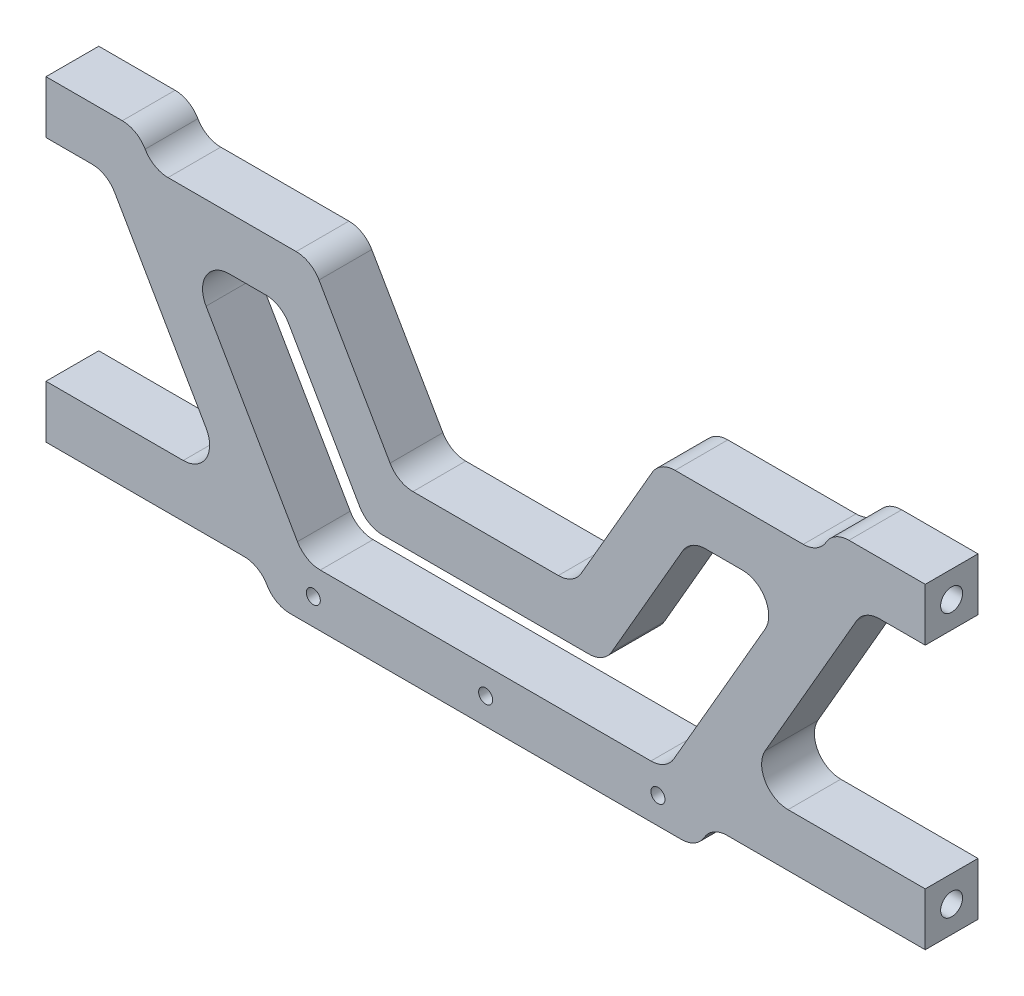
SolidWorks part; units mm, degrees
ref_plane "Front Plane" through (0, 0, 0) normal (0, 0, 1) x (1, 0, 0)
ref_plane "Top Plane" through (0, 0, 0) normal (0, 1, 0) x (1, 0, 0)
ref_plane "Right Plane" through (0, 0, 0) normal (1, 0, 0) x (0, 0, -1)
sketch "Sketch1" plane through (0, 0, 0) normal (0, 0, 1) x (1, 0, 0)
  line L1 (-50, 0) -> (50, 0)
  line L2 (-50, 0) -> (-50, 39)
  line L3 (-50, 39) -> (50, 39)
  line L4 (50, 0) -> (50, 39)
  dimension "D1" = 39
  dimension "D2" = 100
extrude "Boss-Extrude1" add sketch "Sketch1" along normal blind 6
sketch "Sketch2" plane through (0, 0, 6) normal (0, 0, 1) x (1, 0, 0)
  line L0 (-50, 33) -> (-43.0526, 33)
  line L2 (-50, 39) -> (-50, 0) construction
  line L3 (-43.0526, 33) -> (-29.1962, 9)
  line L5 (-29.1962, 9) -> (-50, 9)
  line L6 (-50, 9) -> (-50, 33)
  line L7 (50, 39) -> (-50, 39) construction
  line L8 (-39.5885, 39) -> (-37.8564, 36)
  line L9 (-10, 19) -> (0, 19)
  line L10 (0, 19) -> (0, 39)
  line L11 (0, 39) -> (-39.5885, 39)
  line L12 (-50, 3) -> (-25.7321, 3)
  line L13 (-25.7321, 3) -> (-24, 0)
  line L14 (-50, 0) -> (50, 0) construction
  line L15 (-24, 0) -> (-50, 0)
  line L16 (-50, 0) -> (-50, 3)
  line L17 (-13.4641, 13) -> (0, 13)
  line L18 (0, 13) -> (0, 6)
  line L19 (0, 6) -> (-20.5359, 6)
  line L20 (-20.5359, 6) -> (-34.3923, 30)
  line L21 (-37.8564, 36) -> (-19.815, 36)
  line L22 (-19.815, 36) -> (-10, 19)
  line L23 (-13.4641, 13) -> (-23.2791, 30)
  line L24 (-23.2791, 30) -> (-34.3923, 30)
  dimension "D3" = 60
  dimension "D1" = 6
  dimension "D2" = 24
  dimension "D4" = 6
  dimension "D5" = 3
  dimension "D6" = 24
  dimension "D7" = 6
  dimension "D8" = 6
  dimension "D9" = 3
  dimension "D10" = 6
  dimension "D11" = 6
  dimension "D12" = 20
  dimension "D13" = 10
extrude "Cut-Extrude1" cut sketch "Sketch2" against normal up to next
hole_wizard "Tap Drill for M3 Tap1" positions "Sketch4" profile "Sketch3" hole size "M3" standard "ISO"
sketch "Sketch4" plane through (-50, 0, 0) normal (-1, 0, 0) x (0, 0, 1)
  line L0 (6, 39) -> (0, 39) construction
  line L4 (0, 9) -> (0, 3) construction
  point P0 (3, 36)
  point P2 (3, 6)
  dimension "D1" = 3
  dimension "D2" = 30
  dimension "D3" = 3
sketch "Sketch3" plane through (-50, 36, 3) normal (0, 1, 0) x (0, 0, 1)
  line L0 (0, 0) -> (0, 10.7511)
  line L1 (0, 10.7511) -> (1.25, 10)
  line L2 (1.25, 10) -> (1.25, 0)
  line L5 (1.25, 0) -> (0, 0)
  line L10 (0, 10.7511) -> (-1.25, 10) construction
  line L11 (0, -6.35) -> (0, 107.95) construction
  dimension "Hole Dia." = 2.5
  dimension "Hole Depth" = 10
  dimension "Drill Angle" = 118
fillet "Fillet1" radius 3 12 edges at (-43.0526, 33, 3) (-29.1962, 9, 3) (-24, 0, 3) (-25.7321, 3, 3) (-39.5885, 39, 3) (-20.5359, 6, 3) (-37.8564, 36, 3) (-23.2791, 30, 3) (-19.815, 36, 3) (-34.3923, 30, 3) (-10, 19, 3) (-13.4641, 13, 3)
mirror "Mirror1" about plane through (0, 0, 0) normal (1, 0, 0) of "Fillet1", "Tap Drill for M3 Tap1", "Cut-Extrude1"
hole_wizard "Tap Drill for M2 Tap1" positions "Sketch7" profile "Sketch6" hole size "M2" standard "ISO" end condition up to next
sketch "Sketch7" plane through (0, 0, 6) normal (0, 0, 1) x (1, 0, 0)
  line L0 (-22.2679, 0) -> (22.2679, 0) construction
  point P0 (-19.6, 3)
  point P2 (0, 3)
  point P4 (19.6, 3)
  dimension "D1" = 19.6
  dimension "D2" = 19.6
  dimension "D3" = 3
sketch "Sketch6" plane through (-19.6, 3, 6) normal (1, 0, 0) x (0, -1, 0)
  line L0 (0, 0) -> (0, 6)
  line L1 (0, 6) -> (0.8, 6)
  line L2 (0.8, 6) -> (0.8, 0)
  line L5 (0.8, 0) -> (0, 0)
  line L11 (0, -6.35) -> (0, 107.95) construction
  dimension "Thru Hole Dia." = 1.6
  dimension "Thru Hole Depth" = 6
